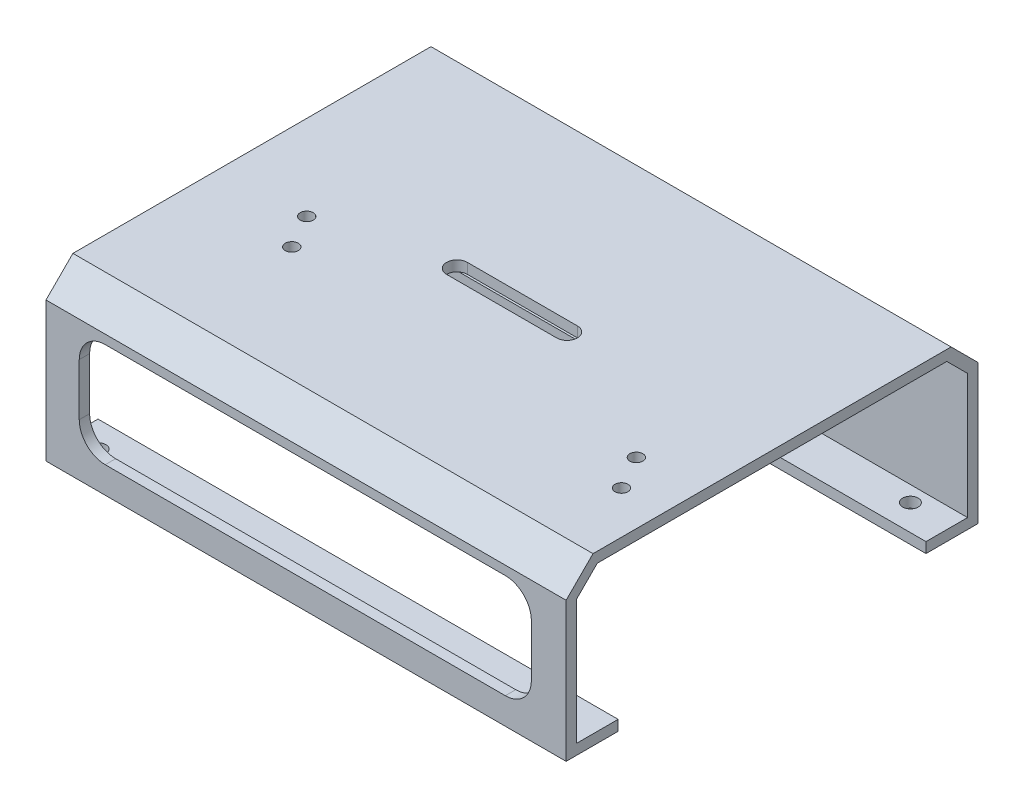
SolidWorks part; units mm, degrees
ref_plane "Front Plane" through (0, 0, 0) normal (0, 0, 1) x (1, 0, 0)
ref_plane "Top Plane" through (0, 0, 0) normal (0, 1, 0) x (1, 0, 0)
ref_plane "Right Plane" through (0, 0, 0) normal (1, 0, 0) x (0, 0, -1)
sketch "Sketch1" plane through (0, 0, 0) normal (1, 0, 0) x (0, 0, -1)
  line L0 (-25.196, -13.0908) -> (-33.196, -13.0908)
  line L2 (-33.196, -13.0908) -> (-33.196, 10.9092)
  line L5 (37.9927, 14.9092) -> (41.9927, 10.9092)
  line L6 (41.9927, 10.9092) -> (41.9927, -13.0908)
  line L20 (41.9927, -13.0908) -> (33.9927, -13.0908)
  line L33 (-33.196, 10.9092) -> (-29.196, 14.9092)
  line L34 (-29.196, 14.9092) -> (37.9927, 14.9092)
  line L41 (-25.196, -15.0908) -> (-35.196, -15.0908)
  line L49 (-35.196, -15.0908) -> (-35.196, 11.7376)
  line L50 (-35.196, 11.7376) -> (-30.0244, 16.9092)
  line L51 (-30.0244, 16.9092) -> (38.8211, 16.9092)
  line L52 (38.8211, 16.9092) -> (43.9927, 11.7376)
  line L56 (43.9927, 11.7376) -> (43.9927, -15.0908)
  line L58 (43.9927, -15.0908) -> (33.9927, -15.0908)
  line L59 (-25.196, -13.0908) -> (-25.196, -15.0908)
  line L60 (33.9927, -13.0908) -> (33.9927, -15.0908)
  dimension "D2" = 24
  dimension "D3" = 4
  dimension "D4" = 4
  dimension "D5" = 2
  dimension "D9" = 8
  dimension "D10" = 8
extrude "Boss-Extrude1" add sketch "Sketch1" along normal blind 100
sketch "Sketch5" plane through (0, -15.0908, 0) normal (0, -1, 0) x (1, 0, 0)
  line L0 (0, 35.196) -> (0, 25.196) construction
  line L1 (100, 35.196) -> (100, 25.196) construction
  line L4 (100, 25.196) -> (0, 25.196) construction
  line L6 (100, -33.9927) -> (0, -33.9927) construction
  line L7 (0, -33.9927) -> (0, -43.9927) construction
  line L8 (100, -33.9927) -> (100, -43.9927) construction
  circle A0 centre (5, 30.196) radius 1.5
  circle A1 centre (92, 30.196) radius 1.5
  circle A2 centre (92, -38.9927) radius 1.5
  circle A3 centre (5, -38.9927) radius 1.5
  dimension "5" = 5
  dimension "D1" = 8
  dimension "D4" = 5
  dimension "D5" = 5
  dimension "D2" = 5
  dimension "D3" = 5
  dimension "D6" = 5
  dimension "D7" = 8
extrude "Cut-Extrude3" cut sketch "Sketch5" against normal blind 4
sketch "Sketch9" plane through (0, 0, 0) normal (0, 1, 0) x (1, 0, 0)
  line L0 (100, 43.9927) -> (104.0587, 43.9927)
  line L1 (100, 43.9927) -> (0, 43.9927) construction
  line L2 (104.0587, 43.9927) -> (104.0587, 38.9927)
  line L3 (104.0587, 38.9927) -> (102, 38.9927)
  line L4 (102, 38.9927) -> (102, 41.9927)
  line L5 (102, 41.9927) -> (100, 41.9927)
  line L6 (100, 43.9927) -> (100, 38.8211) construction
  line L7 (100, 41.9927) -> (100, 43.9927)
  line L8 (100, 38.8211) -> (0, 38.9927) construction
  line L9 (100, 38.8211) -> (100, -30.0244) construction
  line L10 (50, 38.9069) -> (50, -30.0244) construction
  line L11 (-4.0587, 38.9927) -> (-2, 38.9927)
  line L12 (-2, 38.9927) -> (-2, 41.9927)
  line L13 (-2, 41.9927) -> (0, 41.9927)
  line L14 (0, 41.9927) -> (0, 43.9927)
  line L15 (0, 43.9927) -> (-4.0587, 43.9927)
  line L16 (-4.0587, 43.9927) -> (-4.0587, 38.9927)
  line L17 (100, -30.0244) -> (0, -30.0244) construction
  line L18 (50, 4.4413) -> (30.2643, 4.4413) construction
  line L19 (104.0587, -35.1102) -> (104.0587, -30.1102)
  line L20 (104.0587, -30.1102) -> (102, -30.1102)
  line L21 (102, -30.1102) -> (102, -33.1102)
  line L22 (102, -33.1102) -> (100, -33.1102)
  line L23 (100, -33.1102) -> (100, -35.1102)
  line L24 (100, -35.1102) -> (104.0587, -35.1102)
  line L25 (-4.0587, -30.1102) -> (-2, -30.1102)
  line L26 (-2, -30.1102) -> (-2, -33.1102)
  line L27 (-2, -33.1102) -> (0, -33.1102)
  line L28 (0, -33.1102) -> (0, -35.1102)
  line L29 (0, -35.1102) -> (-4.0587, -35.1102)
  line L30 (-4.0587, -35.1102) -> (-4.0587, -30.1102)
  dimension "D1" = 2
  dimension "D2" = 2
  dimension "D3" = 3
sketch "Sketch10" plane through (0, 0, 35.196) normal (0, 0, 1) x (1, 0, 0)
  line L0 (100, -1.6766) -> (83.0146, -1.6766) construction
  line L1 (11.3903, 10) -> (88.3144, 10)
  line L2 (6.3903, 5) -> (6.3903, -5)
  line L3 (11.3903, -10) -> (88.3144, -10)
  line L4 (93.3144, 5) -> (93.3144, -5)
  line L5 (100, 11.7376) -> (100, -15.0908) construction
  arc A0 (88.3144, 10) -> (93.3144, 5) centre (88.3144, 5) cw
  arc A1 (93.3144, -5) -> (88.3144, -10) centre (88.3144, -5) cw
  arc A2 (11.3903, -10) -> (6.3903, -5) centre (11.3903, -5) cw
  arc A3 (6.3903, 5) -> (11.3903, 10) centre (11.3903, 5) cw
  dimension "D3" = 5
  dimension "D1" = 20
  dimension "D2" = 10
extrude "Cut-Extrude5" cut sketch "Sketch10" against normal up to next
sketch "Sketch11" plane through (0, 16.9092, 0) normal (0, 1, 0) x (1, 0, 0)
  line L4 (0, 38.8211) -> (0, -30.0244)
  line L5 (0, -30.0244) -> (100, -30.0244)
  line L6 (100, -30.0244) -> (100, 38.8211)
  line L7 (100, 38.8211) -> (0, 38.8211)
  line L8 (0, 38.8211) -> (0, -30.0244)
  line L9 (0, -30.0244) -> (100, -30.0244)
  line L10 (100, -30.0244) -> (100, 38.8211)
  line L11 (100, 38.8211) -> (0, 38.8211)
  circle A8 centre (19.9718, -7.91) radius 1.25
  circle A9 centre (91.7957, -16.3554) radius 1.25
  circle A15 centre (16.3183, -1.3875) radius 1.25
  circle A16 centre (88.1423, -9.8329) radius 1.25
  dimension "D2" = 2.5
  dimension "D3" = 2.5
  dimension "D5" = 2.5
  dimension "D6" = 2.5
  dimension "D1" = 0
extrude "Cut-Extrude6" cut sketch "Sketch11" against normal up to next contours A9 | A8 | A15 | A16 region at (19.9718, 16.9092, 7.91) region at (91.7957, 16.9092, 16.3554) region at (16.3183, 16.9092, 1.3875) region at (88.1423, 16.9092, 9.8329)
sketch "Sketch7" plane through (0, 16.9092, 0) normal (0, 1, 0) x (1, 0, 0)
  line L0 (100, -30.0244) -> (0, 38.8211) construction
  line L1 (100, 38.8211) -> (100, -30.0244) construction
  line L2 (100, -30.0244) -> (0, -30.0244) construction
  line L3 (100, 38.8211) -> (0, 38.8211) construction
  line L4 (90.6655, 29.8211) -> (91, 29.5909) construction
  line L7 (91, 0.4531) -> (48.6767, 29.5909) construction
  line L8 (89.8659, -1.1942) -> (47.5425, 27.9435)
  line L9 (92.1341, 2.1005) -> (49.8108, 31.2382)
  line L10 (91, -9.2594) -> (91, 29.8211) construction
  line L11 (91, 29.8211) -> (28.3146, 29.8211) construction
  line L12 (58.923, 29.8211) -> (91, 7.7376) construction
  line L13 (60.0571, 31.4685) -> (92.1341, 9.3849)
  line L14 (57.7889, 28.1738) -> (89.8659, 6.0902)
  line L15 (69.5038, 29.8211) -> (91, 15.022) construction
  line L16 (70.638, 31.4685) -> (92.1341, 16.6693)
  line L17 (68.3697, 28.1738) -> (89.8659, 13.3746)
  line L18 (80.0847, 29.8211) -> (91, 22.3064) construction
  line L19 (81.2188, 31.4685) -> (92.1341, 23.9538)
  line L20 (78.9505, 28.1738) -> (89.8659, 20.6591)
  line L21 (91.7996, 31.4685) -> (92.1341, 31.2382)
  line L22 (89.5314, 28.1738) -> (89.8659, 27.9435)
  line L23 (28.3146, 29.8211) -> (9, 29.8211) construction
  line L24 (9, 29.8211) -> (9, -21.0244) construction
  line L25 (9, -21.0244) -> (91, -21.0244) construction
  line L26 (91, -21.0244) -> (91, -9.2594) construction
  line L27 (0, -29.196) -> (0, 37.9927) construction
  line L28 (8.8328, -20.9093) -> (9.1672, -21.1396) construction
  line L29 (9.9669, -19.2619) -> (10.3014, -19.4922)
  line L30 (7.6986, -22.5566) -> (8.0331, -22.7869)
  line L31 (9, -13.74) -> (19.5808, -21.0244) construction
  line L32 (10.1341, -12.0926) -> (20.715, -19.3771)
  line L33 (7.8659, -15.3873) -> (18.4467, -22.6718)
  line L34 (9, -6.4555) -> (30.1617, -21.0244) construction
  line L35 (10.1341, -4.8082) -> (31.2958, -19.3771)
  line L36 (7.8659, -8.1029) -> (29.0275, -22.6718)
  line L37 (9, 0.8289) -> (40.7952, -21.0607) construction
  line L38 (10.1341, 2.4762) -> (41.9293, -19.4133)
  line L39 (7.8659, -0.8185) -> (39.6611, -22.708)
  line L40 (51.3233, -21.0244) -> (9, 8.1133) construction
  line L41 (50.1892, -22.6718) -> (7.8659, 6.466)
  line L42 (52.4575, -19.3771) -> (10.1341, 9.7607)
  line L46 (19.6661, 17.9975) -> (80.976, -24.2117) construction
  line L47 (38.435, 19.6448) -> (95.0171, -19.3094) construction
  line L51 (39.4192, 4.3984) -> (60.5808, 4.3984) construction
  line L52 (39.4192, 6.3984) -> (60.5808, 6.3984)
  line L53 (39.4192, 2.3984) -> (60.5808, 2.3984)
  arc A2 (89.8659, -1.1942) -> (92.1341, 2.1005) centre (91, 0.4531) ccw
  arc A3 (49.8108, 31.2382) -> (47.5425, 27.9435) centre (48.6767, 29.5909) ccw
  arc A4 (60.0571, 31.4685) -> (57.7889, 28.1738) centre (58.923, 29.8211) ccw
  arc A5 (89.8659, 6.0902) -> (92.1341, 9.3849) centre (91, 7.7376) ccw
  arc A6 (70.638, 31.4685) -> (68.3697, 28.1738) centre (69.5038, 29.8211) ccw
  arc A7 (89.8659, 13.3746) -> (92.1341, 16.6693) centre (91, 15.022) ccw
  arc A8 (81.2188, 31.4685) -> (78.9505, 28.1738) centre (80.0847, 29.8211) ccw
  arc A9 (89.8659, 20.6591) -> (92.1341, 23.9538) centre (91, 22.3064) ccw
  arc A10 (91.7996, 31.4685) -> (89.5314, 28.1738) centre (90.6655, 29.8211) ccw
  arc A11 (89.8659, 27.9435) -> (92.1341, 31.2382) centre (91, 29.5909) ccw
  arc A12 (9.9669, -19.2619) -> (7.6986, -22.5566) centre (8.8328, -20.9093) ccw
  arc A13 (8.0331, -22.7869) -> (10.3014, -19.4922) centre (9.1672, -21.1396) ccw
  arc A14 (10.1341, -12.0926) -> (7.8659, -15.3873) centre (9, -13.74) ccw
  arc A15 (18.4467, -22.6718) -> (20.715, -19.3771) centre (19.5808, -21.0244) ccw
  arc A16 (10.1341, -4.8082) -> (7.8659, -8.1029) centre (9, -6.4555) ccw
  arc A17 (29.0275, -22.6718) -> (31.2958, -19.3771) centre (30.1617, -21.0244) ccw
  arc A18 (10.1341, 2.4762) -> (7.8659, -0.8185) centre (9, 0.8289) ccw
  arc A19 (39.6611, -22.708) -> (41.9293, -19.4133) centre (40.7952, -21.0607) ccw
  arc A20 (50.1892, -22.6718) -> (52.4575, -19.3771) centre (51.3233, -21.0244) ccw
  arc A21 (10.1341, 9.7607) -> (7.8659, 6.466) centre (9, 8.1133) ccw
  arc A26 (39.4192, 6.3984) -> (39.4192, 2.3984) centre (39.4192, 4.3984) ccw
  arc A27 (60.5808, 2.3984) -> (60.5808, 6.3984) centre (60.5808, 4.3984) ccw
  arc A28 (19.3544, -3.8715) -> (16.7276, -6.9194) centre (19.5487, -6.6948) ccw
  arc A29 (24.6467, -7.515) -> (22.3784, -10.8097) centre (21.8652, -8.0282) cw
  arc A30 (14.0228, -0.201) -> (17.9115, -2.8781) centre (16.2128, -1.1827) ccw
  point P10 (90.8328, 29.706)
  point P15 (69.8383, 15.022)
  point P27 (74.9615, 18.7794)
  point P32 (80.2519, 22.4216)
  point P41 (85.5423, 26.0638)
  point P53 (9, -21.0244)
  point P61 (14.2904, -17.3822)
  point P66 (19.5808, -13.74)
  point P75 (24.8976, -10.1159)
  point P80 (30.1617, -6.4555)
  point P106 (50, 4.3984)
  dimension "D24" = 2.8284
  dimension "D25" = 2.83
  dimension "D5" = 4
  dimension "D6" = 6
  dimension "D7" = 6
  dimension "D8" = 6
  dimension "D9" = 4
  dimension "D10" = 4
  dimension "D11" = 4
  dimension "D3" = 9
  dimension "D4" = 20
  dimension "D2" = 9
  dimension "4" = 4
  dimension "D12" = 6
  dimension "D13" = 9
  dimension "D14" = 9
  dimension "D15" = 6
  dimension "D16" = 6
  dimension "D17" = 6
  dimension "D18" = 6
  dimension "D19" = 6
  dimension "D20" = 6
  dimension "D21" = 50.8456
  dimension "D22" = 25.4228
  dimension "D23" = 4
extrude "Cut-Extrude4" cut sketch "Sketch7" against normal blind 2 contours L53 A27 L52 A26
equation "\"D5@Sketch5\"=\"D4@Sketch5\""
equation "\"D2@Sketch5\"=\"D4@Sketch5\""
equation "\"D3@Sketch5\"=\"D4@Sketch5\""
equation "\"D6@Sketch5\"=\"5@Sketch5\""
equation "\"D22@Sketch7\"=\"D21@Sketch7\"/2"
